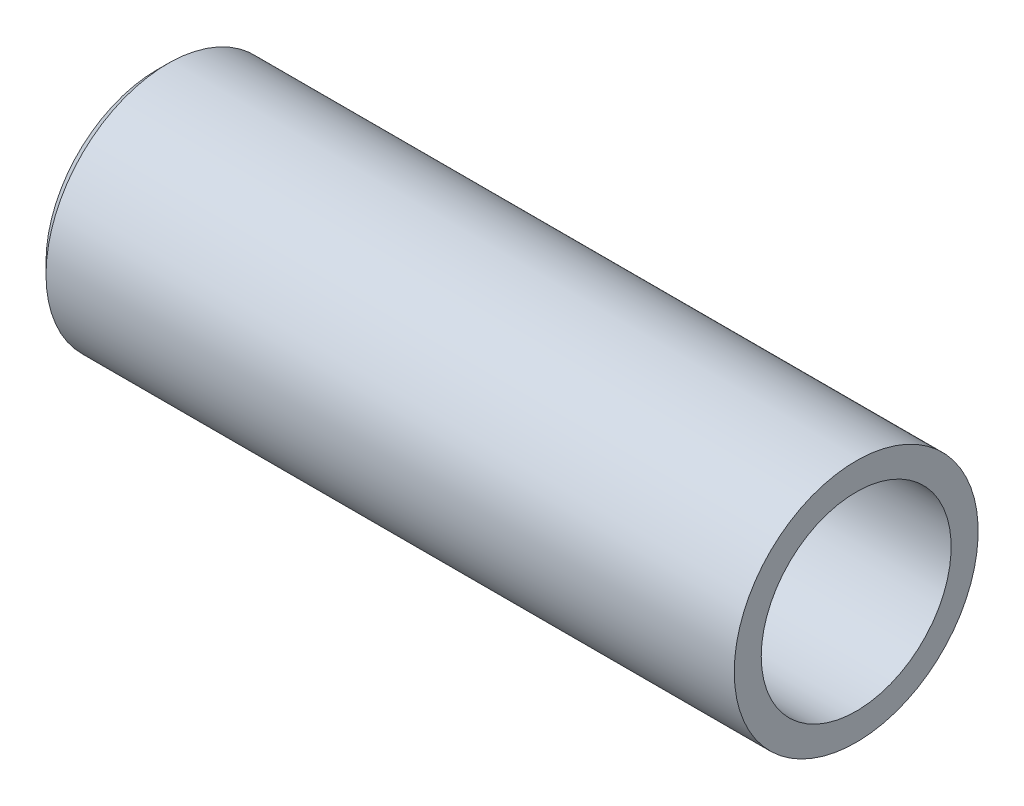
SolidWorks part; units mm, degrees
material "Nylon 6/10"
ref_plane "Front Plane" through (0, 0, 0) normal (0, 0, 1) x (1, 0, 0)
ref_plane "Top Plane" through (0, 0, 0) normal (0, 1, 0) x (1, 0, 0)
ref_plane "Right Plane" through (0, 0, 0) normal (1, 0, 0) x (0, 0, -1)
sketch "Sketch1" plane through (0, 0, 0) normal (0, 0, 1) x (1, 0, 0)
  line L0 (0, 0) -> (22.1407, 0) construction
  line L1 (0.3533, 5.4227) -> (30.9563, 5.4227)
  line L3 (-0.1437, 4.2228) -> (30.9563, 4.2228)
  line L4 (30.9563, 5.4227) -> (30.9563, 4.2228)
  line L5 (30.9563, 11.1125) -> (30.9563, -11.1125) construction
  line L6 (56.8854, 3.9688) -> (-54.7878, 3.9688) construction
  line L7 (-0.1437, -4.1672) -> (-0.1437, 4.1672) construction
  line L8 (-0.1437, 4.2228) -> (-0.1437, 4.9257)
  line L9 (-0.1437, 4.9257) -> (0.3533, 5.4227)
  dimension "D4" = 45
  dimension "D2" = 1.2
  dimension "D1" = 0.254
revolve "Revolve1" add sketch "Sketch1" angle 360 about L0
equation "\"D2@Sketch1\"=1.2mm"
